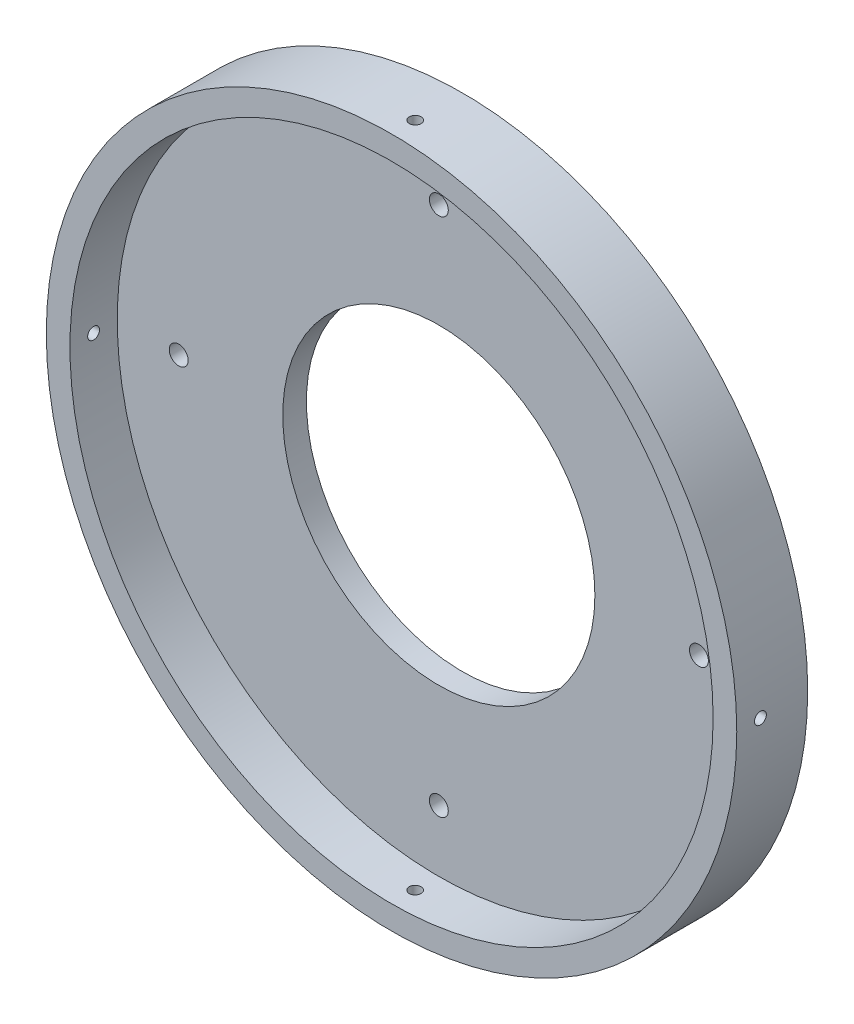
SolidWorks part; units mm, degrees
material "PET"
ref_plane "Front Plane" through (0, 0, 0) normal (0, 0, 1) x (1, 0, 0)
ref_plane "Top Plane" through (0, 0, 0) normal (0, 1, 0) x (1, 0, 0)
ref_plane "Right Plane" through (0, 0, 0) normal (1, 0, 0) x (0, 0, -1)
sketch "Sketch1" plane through (0, 0, 0) normal (0, 0, 1) x (1, 0, 0)
  circle A0 centre (0, 0) radius 73
  circle A1 centre (0, 0) radius 33
  dimension "D1" = 146
  dimension "D2" = 40
extrude "Boss-Extrude1" add sketch "Sketch1" along normal blind 5
sketch "Sketch2" plane through (0, 0, 5) normal (0, 0, 1) x (1, 0, 0)
  circle A0 centre (0, 0) radius 68
  circle A1 centre (0, 0) radius 73
  circle A2 centre (0, 0) radius 73
  dimension "D1" = 0
  dimension "D2" = 5
extrude "Boss-Extrude2" add sketch "Sketch2" along normal blind 10
sketch "Sketch3" plane through (0, 0, 0) normal (0, 1, 0) x (1, 0, 0)
  line L0 (-73, -15) -> (73, -15) construction
  circle A0 centre (0, -10) radius 1.25
  dimension "D2" = 2.5
  dimension "D1" = 5
extrude "Cut-Extrude1" cut sketch "Sketch3" against normal up to surface (73 mm away) up to face at (73, 0, 0)
pattern_circular "CirPattern1" count 4 over 360 about axis through (0, 0, 5) along (0, 0, -1) of "Cut-Extrude1"
sketch "Sketch9" plane through (0, 0, 0) normal (0, 0, -1) x (-1, 0, 0)
  point P0 (0, 55)
  point P4 (55, 0)
  point P6 (0, -55)
  point P8 (-55, 0)
  dimension "D1" = 55
  dimension "D2" = 0
  dimension "D3" = 55
  dimension "D4" = 55
  dimension "D5" = 55
hole_wizard "Ø4.0mm Dowel Hole1" positions "Sketch9" profile "Sketch10" hole size "Ø4.0" standard "ISO" end condition through all
sketch "Sketch10" plane through (0, 55, 0) normal (1, 0, 0) x (0, 1, 0)
  line L0 (0, 0) -> (0, 15)
  line L1 (0, 15) -> (2, 15)
  line L2 (2, 15) -> (2, 0)
  line L5 (2, 0) -> (0, 0)
  line L11 (0, -6.35) -> (0, 107.95) construction
  dimension "Thru Hole Dia." = 4
  dimension "Thru Hole Depth" = 15
